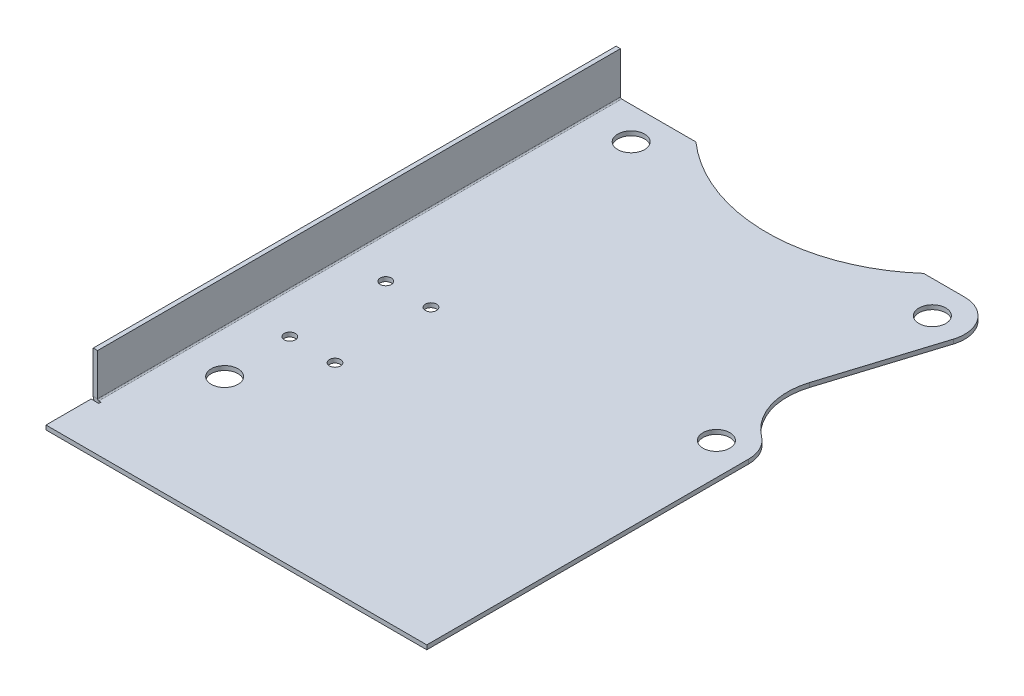
SolidWorks part; units mm, degrees
note: The reader was unsure of these and kept them because the rebuilt part matched: flange length of "Edge-Flange1".
material "PC High Viscosity"
ref_plane "Front Plane" through (0, 0, 0) normal (0, 0, 1) x (1, 0, 0)
ref_plane "Top Plane" through (0, 0, 0) normal (0, 1, 0) x (1, 0, 0)
ref_plane "Right Plane" through (0, 0, 0) normal (1, 0, 0) x (0, 0, -1)
sketch "Sketch1" plane through (0, 0, 0) normal (0, 1, 0) x (1, 0, 0)
  line L0 (109.6195, 311.8073) -> (89.362, 247.1155)
  line L1 (110.49, 0) -> (-114.3, 0)
  line L3 (91.44, 336.55) -> (67.2021, 336.55)
  line L4 (-114.3, 0) -> (-114.3, 336.55)
  line L5 (110.49, 190.0033) -> (110.49, 0)
  line L6 (0, 311.15) -> (0, 336.55) construction
  line L7 (-67.2021, 336.55) -> (-114.3, 336.55)
  arc A0 (109.6195, 311.8073) -> (91.44, 336.55) centre (91.44, 317.5) ccw
  circle A1 centre (91.44, 317.5) radius 7.6886 construction
  arc A2 (110.49, 190.0033) -> (102.867, 205.2456) centre (91.44, 190.0033) ccw
  circle A3 centre (91.44, 190.0033) radius 7.9375 construction
  arc A4 (89.362, 247.1155) -> (102.867, 205.2456) centre (125.721, 235.73) ccw
  arc A5 (-67.2021, 336.55) -> (67.2021, 336.55) centre (0, 412.75) ccw
  circle A7 centre (-86.36, 317.5) radius 7.9375
  circle A8 centre (91.44, 317.5) radius 7.9375
  circle A9 centre (91.44, 190.0033) radius 7.9375
  circle A10 centre (-86.36, 77.5033) radius 7.9375
  circle A11 centre (-60.8584, 173.7876) radius 3.302
  circle A12 centre (-60.8584, 173.7876) radius 3.302 construction
  circle A13 centre (-87.5284, 173.7876) radius 3.302
  circle A14 centre (-87.5284, 173.7876) radius 3.302 construction
  circle A15 centre (-60.8584, 117.1456) radius 3.302
  circle A16 centre (-60.8584, 117.1456) radius 3.302 construction
  circle A17 centre (-87.5284, 117.1456) radius 3.302
  circle A18 centre (-87.5284, 117.1456) radius 3.302 construction
  point P0 (0, 0)
  dimension "D1" = 38.1
  dimension "D3" = 76.2
  dimension "D4" = 25.4
  dimension "D5" = 101.6
  dimension "D2" = 114.3
base flange "Base-Flange1" sketch "Sketch1" thickness 2.54 reverse thickness direction no parameters "D1"=0.7366
edge flange "Edge-Flange1" sketch "Sketch4" flange angle 90 flange length 27.94 flange position material inside bend radius 0.7366 thickness 2.54 relief rectangular parameters "D6"=10
sketch "Sketch4" plane through (-114.3, 0, 0) normal (1, 0, 0) x (0, 0, -1)
  line L2 (27.8765, 0) -> (27.8765, 25.4)
  line L3 (27.8765, 25.4) -> (336.55, 25.4)
  line L4 (336.55, 25.4) -> (336.55, 0)
  line L5 (336.55, 0) -> (0, 0) construction
  line L6 (336.55, 0) -> (27.8765, 0)
  line L9 (27.8765, 27.94) -> (27.8765, 0.7874) construction
  line L10 (25.3365, 12.7762) -> (25.3365, 14.7701) construction
  dimension "D1" = 2.54
  dimension "D2" = 25.4
bend "EdgeBend2" [suppressed] bend radius 0.7366 bend angle 90 parameters "D5"=1
edge flange "Edge-Flange2" [suppressed] sketch "Sketch9" flange angle 90 flange position material inside bend radius 0.7366 thickness 2.54
sketch "Sketch9" [suppressed] plane through (-114.3, -2.54, 0) normal (1, 0, 0) x (0, 0, 1)
  line L2 (-336.55, 0) -> (-336.55, 22.86)
  line L3 (-336.55, 22.86) -> (-24.3933, 22.86)
  line L4 (-24.3933, 22.86) -> (-24.3933, 0)
  line L5 (0, 0) -> (-336.55, 0) construction
  line L6 (-24.3933, 0) -> (-336.55, 0)
bend "EdgeBend3" [suppressed] bend radius 0.7366 bend angle 90 parameters "D5"=1, "D6"=10, "D7"=25.4
sketch "Bend-Lines1" [suppressed] plane through (0, 0, 0) normal (0, 1, 0) x (1, 0, 0)
sketch "Bounding-Box1" [suppressed] plane through (0, 0, 0) normal (0, 1, 0) x (1, 0, 0)
sheet metal parameters "Sheet-Metal1" thickness 2.54 parameters "D1"=0.7366
flat pattern "Flat-Pattern1" [suppressed]
sketch "Bend-Lines2" plane through (0, 0, 0) normal (0, 1, 0) x (1, 0, 0)
sketch3d "Bounding-Box2" [suppressed]
  line L0 (-204.0394, 19.05, 0) -> (-204.0394, -317.5, 0) construction
  line L1 (19.05, 19.05, 0) -> (19.05, -317.5, 0) construction
  line L2 (-204.0394, 19.05, 0) -> (19.05, 19.05, 0) construction
  line L3 (-204.0394, -317.5, 0) -> (19.05, -317.5, 0) construction
sheet metal parameters "Sheet-Metal2" [suppressed] thickness 2.54 parameters "D1"=0.7366
flat pattern "Flat-Pattern1"
sketch "Bend-Lines2" plane through (0, 0, 0) normal (0, 1, 0) x (1, 0, 0)
sketch3d "Bounding-Box2" [suppressed]
  line L0 (-226.0381, 19.05, 0) -> (-226.0381, -317.5, 0) construction
  line L1 (19.05, 19.05, 0) -> (19.05, -317.5, 0) construction
  line L2 (-226.0381, 19.05, 0) -> (19.05, 19.05, 0) construction
  line L3 (-226.0381, -317.5, 0) -> (19.05, -317.5, 0) construction
bend of the flat pattern "Flatten-<EdgeBend2>1"
sheet metal parameters "Sheet-Metal3" [suppressed] thickness 2.54 parameters "D1"=0.7366
flat pattern "Flat-Pattern1"
sketch "Bend-Lines2" plane through (0, 0, 0) normal (0, 1, 0) x (1, 0, 0)
  line L0 (-112.5994, 336.55) -> (-112.5994, 24.3933) construction
  line L1 (-112.5994, 336.55) -> (-112.5994, 24.3933) construction
sketch3d "Bounding-Box2" [suppressed]
  line L0 (-227.7388, 146.5467, 0) -> (-227.7388, -190.0033, 0) construction
  line L1 (19.05, 146.5467, 0) -> (19.05, -190.0033, 0) construction
  line L2 (-227.7388, 146.5467, 0) -> (19.05, 146.5467, 0) construction
  line L3 (-227.7388, -190.0033, 0) -> (19.05, -190.0033, 0) construction
bend of the flat pattern "Flatten-<EdgeBend3>1"
